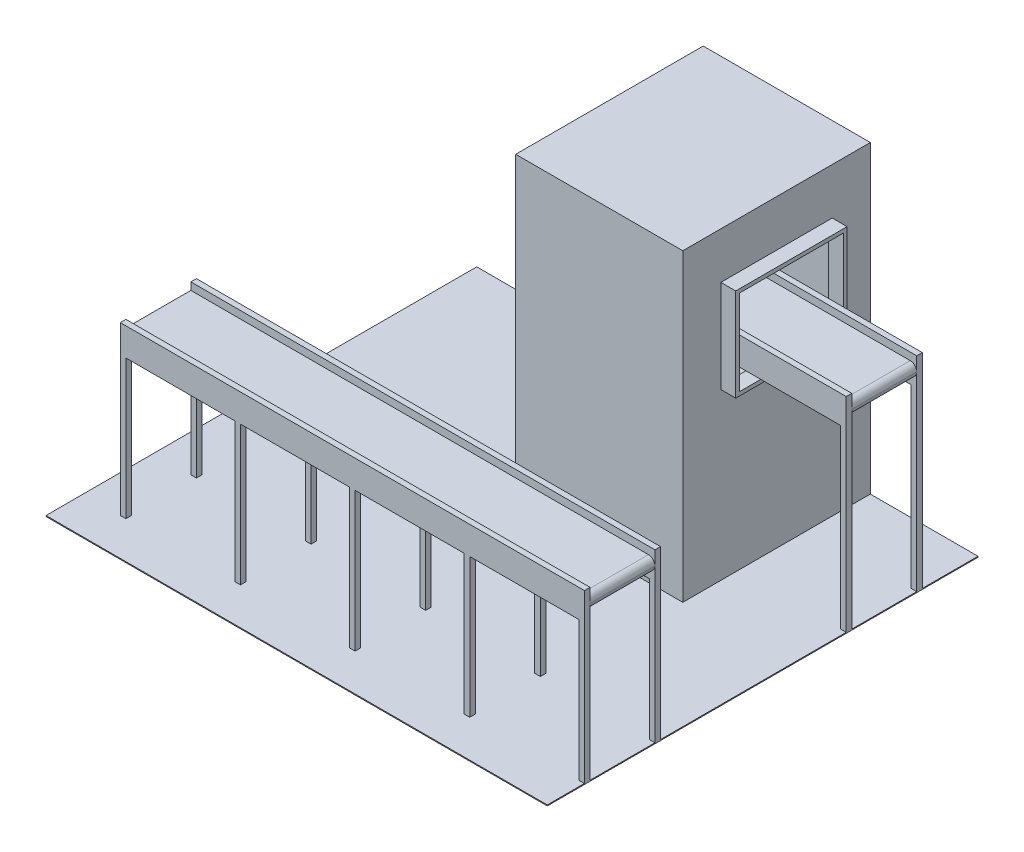
SolidWorks part; units mm, degrees
ref_plane "Front Plane" through (0, 0, 0) normal (0, 0, 1) x (1, 0, 0)
ref_plane "Top Plane" through (0, 0, 0) normal (0, 1, 0) x (1, 0, 0)
ref_plane "Right Plane" through (0, 0, 0) normal (1, 0, 0) x (0, 0, -1)
sketch "Sketch1" plane through (0, 0, 0) normal (1, 0, 0) x (0, 0, -1)
  line L1 (1615, 0) -> (1110, 0)
  line L2 (0, 0) -> (0, 900)
  line L3 (0, 900) -> (410, 900)
  line L5 (1615, 0) -> (1615, 800)
  line L7 (1615, 0) -> (2120, 0)
  line L11 (1615, 800) -> (1410, 800)
  line L13 (1410, 0) -> (1410, 800)
  line L14 (1410, 800) -> (1410, 1100)
  line L15 (1410, 1100) -> (1820, 1100)
  line L16 (1820, 1100) -> (1820, 0)
  line L17 (1790, 550) -> (1790, 0)
  line L18 (1820, 1100) -> (1820, 950)
  line L19 (1410, 950) -> (1440, 950)
  line L20 (1410, 950) -> (1410, 1100)
  line L21 (410, 900) -> (410, 750)
  line L22 (410, 750) -> (0, 750)
  line L23 (410, 750) -> (410, 0)
  line L24 (1615, 950) -> (1915, 950)
  line L25 (1615, 1100) -> (1615, 1150)
  line L26 (1440, 950) -> (1440, 1100)
  line L27 (1440, 950) -> (1440, 0)
  line L28 (1790, 0) -> (1820, 0)
  line L29 (1440, 950) -> (1615, 950)
  line L30 (1820, 550) -> (1790, 550)
  line L31 (1790, 550) -> (1790, 950)
  line L32 (30, 450) -> (30, 750)
  line L33 (30, 450) -> (30, 0)
  line L34 (380, 375) -> (380, 750)
  line L35 (380, 375) -> (380, 0)
  line L36 (1790, 0) -> (1615, 0)
  line L37 (1790, 950) -> (1790, 1100)
  line L38 (380, 750) -> (380, 900)
  line L39 (30, 750) -> (30, 900)
  line L40 (1615, 1100) -> (1615, 1060)
  line L41 (1615, 1060) -> (1440, 1060)
  line L42 (1615, 1060) -> (1790, 1060)
  line L43 (0, 0) -> (30, 0)
  line L44 (205, 860) -> (380, 860)
  line L45 (205, 860) -> (30, 860)
  line L46 (30, 0) -> (380, 0)
  line L47 (380, 0) -> (410, 0)
  line L48 (410, 0) -> (1110, 0)
  line L49 (1615, 950) -> (1615, 990)
  line L50 (1615, 990) -> (1440, 990)
  line L51 (1440, 990) -> (1615, 990)
  line L52 (1790, 990) -> (1615, 990)
  line L53 (205, 750) -> (205, 790)
  line L54 (205, 790) -> (30, 790)
  line L55 (205, 790) -> (380, 790)
  dimension "D2" = 900
  dimension "D3" = 1000
  dimension "D4" = 150
  dimension "D5" = 150
extrude "Boss-Extrude5" add sketch "Sketch1" against normal blind 30 contours L16 L30 L17 L7 | L31 L30 L16 L24 | L27 L19 L14 L11 | L27 L11 L13 L1 region at (0, 400, -1425) region at (0, 275, -1805) region at (0, 875, -1425) region at (0, 750, -1805)
extrude "Boss-Extrude6" add sketch "Sketch1<10>" against normal blind 500 contours L19 L26 L15 L14 | L52 L37 L42 L41 L26 L50 | L37 L24 L16 L15 region at (0, 1025, -1425) region at (0, 1025, -1805) region at (0, 1025, -1615)
sketch "Sketch1<10>" plane through (0, 0, 0) normal (1, 0, 0) x (0, 0, -1) same geometry as "Sketch1"
extrude "Boss-Extrude7" add sketch "Sketch1<11>" against normal blind 2500 separate body contours L35 L47 L23 L22 L34 | L2 L43 L33 L32 L22 | L22 L39 L3 L2 | L54 L55 L38 L44 L45 L39 | L38 L22 L21 L3 region at (0, 375, -395) region at (0, 825, -395) region at (0, 375, -15) region at (0, 825, -205) region at (0, 825, -15)
sketch "Sketch1<11>" plane through (0, 0, 0) normal (1, 0, 0) x (0, 0, -1) same geometry as "Sketch1"
sketch "Sketch2" plane through (-500, 0, 0) normal (-1, 0, 0) x (0, 0, 1)
  line L4 (-1615, 890) -> (-1315, 890)
  line L5 (-1315, 890) -> (-1315, 1390)
  line L6 (-1615, 890) -> (-1915, 890)
  line L7 (-1915, 890) -> (-1915, 1390)
  line L8 (-1915, 1390) -> (-1315, 1390)
  line L13 (-1335, 910) -> (-1895, 910)
  line L14 (-1895, 910) -> (-1895, 1370)
  line L15 (-1895, 1370) -> (-1335, 1370)
  line L16 (-1335, 1370) -> (-1335, 910)
extrude "Boss-Extrude8" add sketch "Sketch2" along normal blind 80 separate body
sketch "Sketch6" plane through (-580, 0, 0) normal (-1, 0, 0) x (0, 0, 1)
  line L0 (-1915, 890) -> (-1315, 890)
  line L3 (-1315, 890) -> (-1315, 1390)
  line L4 (-1110, 1140) -> (-1110, 1640)
  line L5 (-1110, 1640) -> (-2120, 1640)
  line L6 (-2120, 1640) -> (-2120, 0)
  line L7 (-2120, 0) -> (-1110, 0)
  line L8 (-1110, 0) -> (-1110, 1140)
  line L9 (-1315, 1390) -> (-1915, 1390)
  line L10 (-1915, 1390) -> (-1915, 890)
extrude "Boss-Extrude10" add sketch "Sketch6" along normal blind 900 contours L4 L5 L6 L7 L8
extrude "Cut-Extrude2" cut sketch "Sketch6<4>" along normal through all flip side to cut
sketch "Sketch6<4>" plane through (-580, 0, 0) normal (-1, 0, 0) x (0, 0, 1) same geometry as "Sketch6"
fillet "Fillet1" radius 35 2 edges at (0, 990, -1615) (0, 1060, -1615)
fillet "Fillet2" radius 35 2 edges at (0, 790, -205) (0, 860, -205)
sketch "Sketch17" plane through (-500, 0, 0) normal (-1, 0, 0) x (0, 0, 1)
  line L0 (-1615, 1060) -> (-1440, 1060)
  line L1 (-1440, 1060) -> (-1790, 1060) construction
  line L2 (-1440, 1060) -> (-1440, 1100)
  line L3 (-1440, 1100) -> (-1410, 1100)
  line L4 (-1410, 1100) -> (-1410, 950)
  line L5 (-1410, 950) -> (-1440, 950)
  line L6 (-1440, 950) -> (-1440, 990)
  line L7 (-1440, 990) -> (-1790, 990)
  line L8 (-1790, 990) -> (-1790, 950)
  line L9 (-1790, 950) -> (-1790, 990) construction
  line L10 (-1790, 950) -> (-1820, 950)
  line L11 (-1820, 950) -> (-1820, 1100)
  line L12 (-1820, 1100) -> (-1790, 1100)
  line L13 (-1790, 1100) -> (-1790, 1060)
  line L14 (-1790, 1060) -> (-1615, 1060)
extrude "Boss-Extrude11" add sketch "Sketch17" along normal blind 1000
sketch "Sketch19" plane through (0, 0, -410) normal (0, 0, -1) x (-1, 0, 0)
  line L0 (0, 0) -> (30, 0)
  line L1 (2500, 0) -> (0, 0) construction
  line L2 (0, 900) -> (0, 750)
  line L3 (0, 900) -> (0, 0) construction
  line L4 (0, 750) -> (30, 750)
  line L5 (30, 750) -> (30, 0)
  line L6 (2500, 0) -> (2470, 0)
  line L7 (2470, 0) -> (2470, 750)
  line L8 (30, 750) -> (1235, 750)
  line L9 (1250, 750) -> (1250, 0)
  line L10 (1250, 0) -> (1265, 0)
  line L11 (1250, 0) -> (1235, 0)
  line L12 (1235, 0) -> (1235, 750)
  line L13 (1265, 0) -> (1265, 750)
  line L14 (632.5, 750) -> (632.5, 0)
  line L15 (632.5, 0) -> (617.5, 0)
  line L16 (632.5, 0) -> (647.5, 0)
  line L17 (647.5, 0) -> (647.5, 750)
  line L18 (617.5, 0) -> (617.5, 750)
  line L19 (1265, 750) -> (2470, 750)
  line L20 (1867.5, 750) -> (1867.5, 0)
  line L21 (1867.5, 0) -> (1882.5, 0)
  line L22 (1867.5, 0) -> (1852.5, 0)
  line L23 (1852.5, 0) -> (1852.5, 750)
  line L24 (1882.5, 0) -> (1882.5, 750)
  line L25 (30, 0) -> (2470, 0)
  line M12 (0, 0) -> (2500, 0)
extrude "Cut-Extrude3" cut sketch "Sketch19" against normal blind 2000 contours L18 L8 L5 M12 | L17 L12 L8 M12 | L23 L19 L13 M12 | L24 L7 L19 M12 region at (-323.75, 375, -410) region at (-1558.75, 375, -410) region at (-941.25, 375, -410) region at (-2176.25, 375, -410)
sketch "Sketch20" plane through (0, 0, 0) normal (0, -1, 0) x (1, 0, 0)
  line L0 (0, 0) -> (0, -1820)
  line L1 (-580, -2120) -> (0, -2120)
  line L2 (0, -2120) -> (0, -1820)
  line L3 (0, 0) -> (0, 200)
  line L4 (0, 200) -> (-2700, 200)
  line L5 (-2700, 200) -> (-2700, -2120)
  line L6 (-2700, -2120) -> (0, -2120)
  line M3 (-580, -2120) -> (-580, -1110)
  line M4 (-580, -1110) -> (-1480, -1110)
  line M5 (-1480, -1110) -> (-1480, -2120)
  line M6 (-1480, -2120) -> (-580, -2120)
extrude "Boss-Extrude12" add sketch "Sketch20" along normal blind 5 contours L5 L6 L1 L2 L0 L3 L4 M5 M4 M3 | M6 M3 M4 M5 region at (-1404.3193, 0, -848.8151) region at (-1030, 0, -1615)
